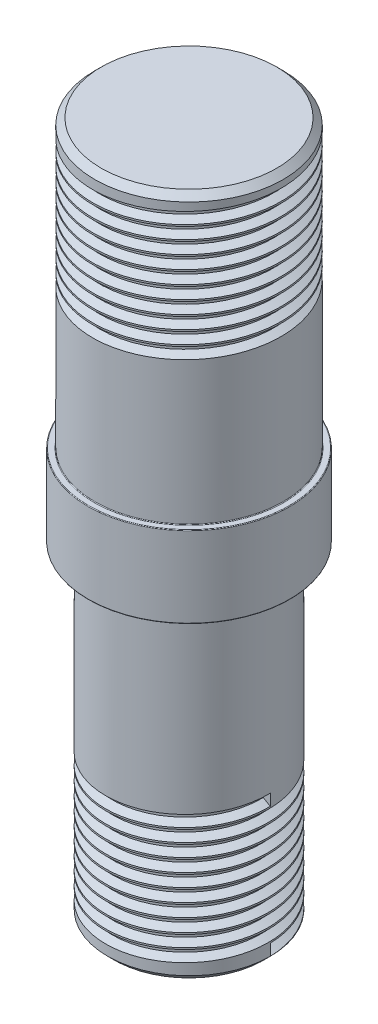
SolidWorks part; units mm, degrees
ref_plane "Płaszczyzna przednia" through (0, 0, 0) normal (0, 0, 1) x (1, 0, 0)
ref_plane "Płaszczyzna górna" through (0, 0, 0) normal (0, 1, 0) x (1, 0, 0)
ref_plane "Płaszczyzna prawa" through (0, 0, 0) normal (1, 0, 0) x (0, 0, -1)
sketch "Szkic1" plane through (0, 0, 0) normal (0, 0, 1) x (1, 0, 0)
  line L0 (0, 0) -> (0, 106.5) construction
  line L1 (0, 0) -> (11.5, 0)
  line L2 (12.5, 1) -> (12.5, 49.9)
  line L3 (12.6, 50) -> (15.4, 50)
  line L4 (15.5, 50.1) -> (15.5, 62.4)
  line L5 (15.4, 62.5) -> (14.6, 62.5)
  line L6 (14.5, 62.6) -> (14.5, 105.5)
  line L7 (13.5, 106.5) -> (0, 106.5)
  line L8 (14.5, 105.5) -> (13.5, 106.5)
  line L9 (11.5, 0) -> (12.5, 1)
  line L10 (0, 0) -> (0, 106.5)
  arc A0 (15.4, 50) -> (15.5, 50.1) centre (15.4, 50.1) ccw
  arc A1 (15.5, 62.4) -> (15.4, 62.5) centre (15.4, 62.4) ccw
  arc A2 (14.5, 62.6) -> (14.6, 62.5) centre (14.6, 62.6) ccw
  arc A3 (12.5, 49.9) -> (12.6, 50) centre (12.6, 49.9) cw
  point P5 (12.5, 0)
  point P10 (14.5, 106.5)
  point P16 (15.5, 50)
  point P19 (15.5, 62.5)
  point P22 (14.5, 62.5)
  point P25 (12.5, 50)
  dimension "D8" = 0.1
  dimension "D1" = 12.5
  dimension "D2" = 50
  dimension "D3" = 3
  dimension "D4" = 12.5
  dimension "D5" = 1
  dimension "D6" = 44
  dimension "D7" = 14.5
revolve "Obrót1" add sketch "Szkic1" angle 360 about L0
thread "Gwint1" pitch 2 method cut profile "Profil gwintu1" start angle 0, offset 0, length 20, pitch 2, diameter 29
ref_plane "Płaszczyzna4" through (-14.5, 105.5, 0) normal (0, 0, 1) x (-1, 0, 0)
sketch "Profil gwintu1" plane through (-14.5, 105.5, 0) normal (0, 0, 1) x (-1, 0, 0)
  line L0 (0, 0) -> (0, 2) construction
  line L11 (0, 0) -> (0, 1.75)
  line L12 (0, 1.75) -> (-1.0825, 1.125)
  line L13 (-1.0825, 1.125) -> (-1.0825, 0.625)
  line L15 (-1.0825, 0.625) -> (0, 0)
  line L17 (-1.0825, 0.875) -> (0, 0.875) construction
  point P2 (0, 0)
  dimension "Pitch" = 2
  dimension "Profile_Angle" = 60
  dimension "Profile_Land" = 0.5
  dimension "Profile_Height" = 1.0825
thread "Gwint2" pitch 2 method cut profile "Profil gwintu2" start angle 0, offset 0, length 20, pitch 2, diameter 25
ref_plane "Płaszczyzna5" through (12.5, 1, 0) normal (0, 0, 1) x (1, 0, 0)
sketch "Profil gwintu2" plane through (12.5, 1, 0) normal (0, 0, 1) x (1, 0, 0)
  line L0 (0, 0) -> (0, 2) construction
  line L11 (0, 0) -> (0, 1.75)
  line L12 (0, 1.75) -> (-1.0825, 1.125)
  line L13 (-1.0825, 1.125) -> (-1.0825, 0.625)
  line L15 (-1.0825, 0.625) -> (0, 0)
  line L17 (-1.0825, 0.875) -> (0, 0.875) construction
  point P2 (0, 0)
  dimension "Pitch" = 2
  dimension "Profile_Angle" = 60
  dimension "Profile_Land" = 0.5
  dimension "Profile_Height" = 1.0825
